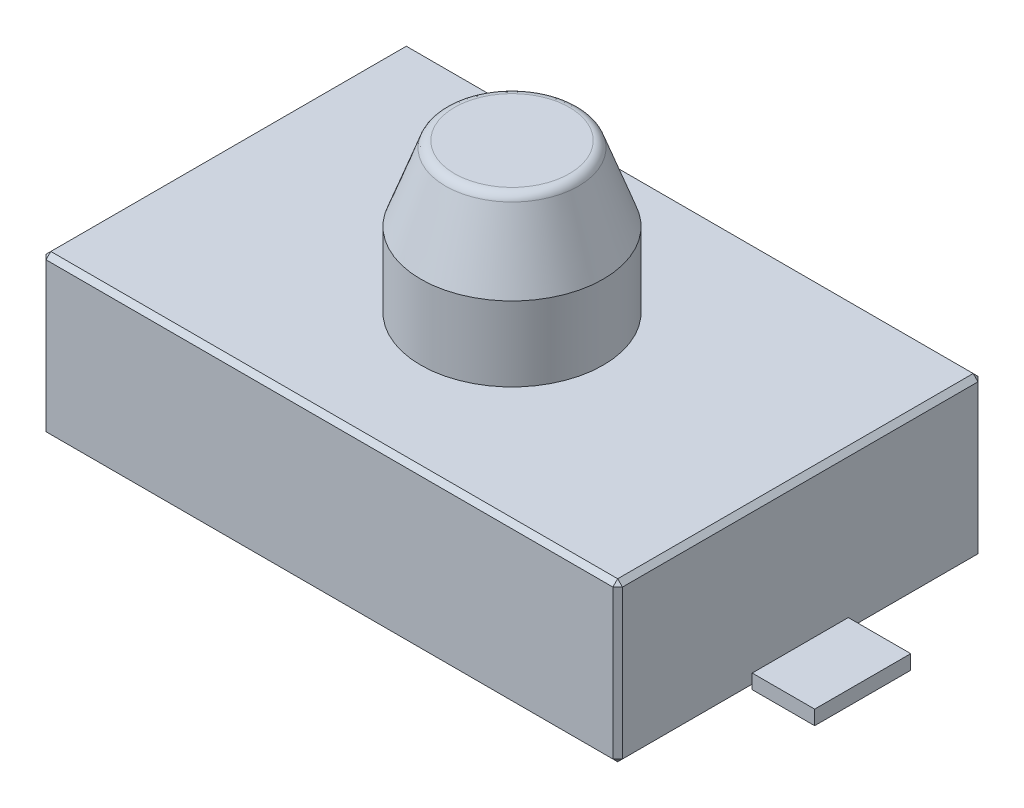
SolidWorks part; units mm, degrees
ref_plane "Front Plane" through (0, 0, 0) normal (0, 0, 1) x (1, 0, 0)
ref_plane "Top Plane" through (0, 0, 0) normal (0, 1, 0) x (1, 0, 0)
ref_plane "Right Plane" through (0, 0, 0) normal (1, 0, 0) x (0, 0, -1)
sketch "Sketch1" plane through (0, 0, 0) normal (0, 1, 0) x (1, 0, 0)
  line L0 (-1.5499, 0.224) -> (-1.5499, -3.576) construction
  line L1 (-4.5499, -3.576) -> (1.4501, -3.576)
  line L2 (-4.5499, -3.576) -> (-4.5499, 0.224)
  line L3 (-4.5499, 0.224) -> (1.4501, 0.224)
  line L4 (1.4501, -3.576) -> (1.4501, 0.224)
  line L5 (-4.5499, -3.576) -> (1.4501, 0.224) construction
  line L6 (-4.5499, 0.224) -> (1.4501, -3.576) construction
  line L7 (-4.5499, -1.676) -> (1.4501, -1.676) construction
  line L8 (1.4501, -2.176) -> (2.1001, -2.176)
  line L9 (-4.5499, -1.176) -> (-5.1999, -1.176)
  line L10 (-4.5499, -1.176) -> (-4.5499, -2.176)
  line L11 (-4.5499, -2.176) -> (-5.1999, -2.176)
  line L12 (-5.1999, -1.176) -> (-5.1999, -2.176)
  line L13 (2.1001, -1.176) -> (2.1001, -2.176)
  line L14 (1.4501, -1.176) -> (2.1001, -1.176)
  line L15 (1.4501, -1.176) -> (1.4501, -2.176)
  point P0 (-1.5499, -1.676)
  point P13 (0, 0)
  dimension "D1" = 6
  dimension "D2" = 3.8
  dimension "D3" = 1
  dimension "D4" = 0.65
extrude "Boss-Extrude1" add sketch "Sketch1" along normal blind 1.65 contours L1 L4 L3 L2
extrude "Boss-Extrude2" add sketch "Sketch1<3>" along normal blind 0.15 separate body contours L8 L13 L14 L15 | L11 L12 L9 L10
sketch "Sketch1<3>" plane through (0, 0, 0) normal (0, 1, 0) x (1, 0, 0) same geometry as "Sketch1"
sketch "Sketch2" plane through (0, 1.65, 0) normal (0, 1, 0) x (1, 0, 0)
  circle A0 centre (-1.5499, -1.676) radius 0.95
  point P0 (-1.5499, -1.676)
  dimension "D1" = 1.9
extrude "Boss-Extrude3" add sketch "Sketch2" along normal blind 0.775 separate body
sketch "Sketch4" plane through (0, 2.425, 0) normal (0, 1, 0) x (1, 0, 0)
  circle A0 centre (-1.5499, -1.676) radius 0.95 construction
  circle A1 centre (-1.5499, -1.676) radius 0.95
extrude "Boss-Extrude4" add sketch "Sketch4" along normal blind 0.775 draft 20
fillet "Fillet1" radius 0.1 1 edges at (-1.5499, 3.2, 2.3439)
chamfer "Chamfer1" distance 0.05 12 edges at (1.4501, 0, 1.676) (-4.5499, 0, 1.676) (1.4501, 0.825, -0.224) (-1.5499, 0, -0.224) (-4.5499, 0.825, -0.224) (-4.5499, 0.825, 3.576) (-1.5499, 0, 3.576) (1.4501, 0.825, 3.576) (-1.5499, 1.65, -0.224) (1.4501, 1.65, 1.676) (-1.5499, 1.65, 3.576) (-4.5499, 1.65, 1.676)
